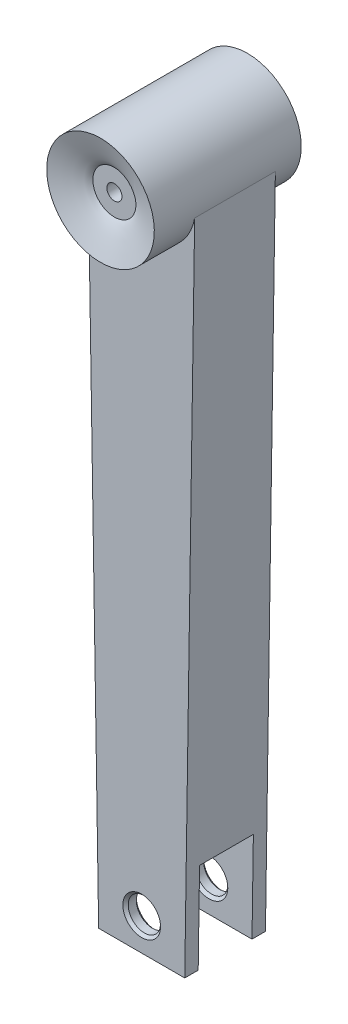
SolidWorks part; units mm, degrees
material "PE 高密度"
ref_plane "前视基准面" through (0, 0, 0) normal (0, 0, 1) x (1, 0, 0)
ref_plane "上视基准面" through (0, 0, 0) normal (0, 1, 0) x (1, 0, 0)
ref_plane "右视基准面" through (0, 0, 0) normal (1, 0, 0) x (0, 0, -1)
other "Configuration Table"
sketch "草图1" plane through (0, 0, 0) normal (0, 0, 1) x (1, 0, 0)
  circle A0 centre (0, 0) radius 10
  dimension "D1" = 20
extrude "凸台-拉伸1" add sketch "草图1" along normal blind 28
ref_plane "基准面1" through (0, 0, 20) normal (0, 0, 1) x (1, 0, 0)
sketch "草图2" plane through (0, 0, 20) normal (0, 0, 1) x (1, 0, 0)
  line L0 (-9.9987, -0.1601) -> (-8, -125)
  line L1 (-8, -125) -> (8, -125)
  line L2 (0, 0) -> (0, -125) construction
  line L3 (9.8429, -1.7658) -> (8, -125)
  circle A1 centre (0, 0) radius 10
  arc A2 (-9.9987, -0.1601) -> (9.8429, -1.7658) centre (0, 0) ccw
  point P12 (0, -125)
  dimension "D2" = 16
  dimension "D3" = 125
  dimension "D1" = 0
extrude "凸台-拉伸2" add sketch "草图2" against normal blind 15
ref_plane "基准面2" through (0, 0, 14) normal (0, 0, -1) x (-1, 0, 0)
ref_plane "基准面3" through (0, 0, 3.76) normal (0, 0, -1) x (-1, 0, 0)
sketch "草图3" plane through (0, 0, 3.76) normal (0, 0, -1) x (-1, 0, 0)
  circle A0 centre (0, 0) radius 4
  dimension "D1" = 8
sketch "草图4" plane through (0, 0, 0) normal (0, 0, -1) x (-1, 0, 0)
  circle A0 centre (0, 0) radius 11
  dimension "D1" = 22
extrude "切除-拉伸2" cut sketch "草图3" against normal through all both and the other way through all
loft "切除-放样2" cut profiles "草图3<2>", "草图4" connector at (3.2913, -2.2732, 3.76) connector at (6.4712, 8.8951, 0)
sketch "草图3<2>" plane through (0, 0, 3.76) normal (0, 0, -1) x (-1, 0, 0) same geometry as "草图3"
mirror "镜向1" about plane through (0, 0, 14) normal (0, 0, -1) of "切除-放样2"
sketch "草图7" plane through (0, 0, 0) normal (1, 0, 0) x (0, 0, -1)
  line L0 (-12.5, -119) -> (-12.5, -118.0885) construction
  line L1 (-17.5, -108) -> (-7.5, -108)
  line L2 (-17.5, -108) -> (-17.5, -130)
  line L3 (-17.5, -130) -> (-7.5, -130)
  line L4 (-7.5, -108) -> (-7.5, -130)
  line L5 (-17.5, -108) -> (-7.5, -130) construction
  line L6 (-17.5, -130) -> (-7.5, -108) construction
  line L7 (-20, -125) -> (-20, -1.7658) construction
  line L9 (-5, -125) -> (-20, -125) construction
  point P0 (-12.5, -119)
  dimension "D1" = 7.5
  dimension "D2" = 10
  dimension "D3" = 17
  dimension "D4" = 5
extrude "切除-拉伸3" cut sketch "草图7" against normal through all both and the other way through all
sketch "草图8" plane through (0, 0, 5) normal (0, 0, -1) x (-1, 0, 0)
  line L0 (8, -125) -> (-8, -125) construction
  circle A0 centre (0, -119) radius 3
  dimension "D1" = 6
  dimension "D2" = 6
  dimension "D3" = 8
extrude "切除-拉伸4" cut sketch "草图8" against normal through all and the other way through all
ref_plane "基准面4" through (0, 0, 25.0722) normal (0, 0, 1) x (1, 0, 0)
sketch "草图9" plane through (0, 0, 25.0722) normal (0, 0, 1) x (1, 0, 0)
  circle A0 centre (0, 0) radius 4 construction
  circle A1 centre (0, 0) radius 4
extrude "凸台-拉伸3" add sketch "草图9" against normal blind 3
sketch "草图10" plane through (0, 0, 22.0722) normal (0, 0, -1) x (-1, 0, 0)
  circle A0 centre (0, 0) radius 1.4
  dimension "D1" = 2.8
extrude "切除-拉伸5" cut sketch "草图10" against normal through all
chamfer "倒角1" distance 0.5 angle 45 4 edges at (3, -119, 5) (0, -116, 7.5) (0, -122, 17.5) (3, -119, 20)
